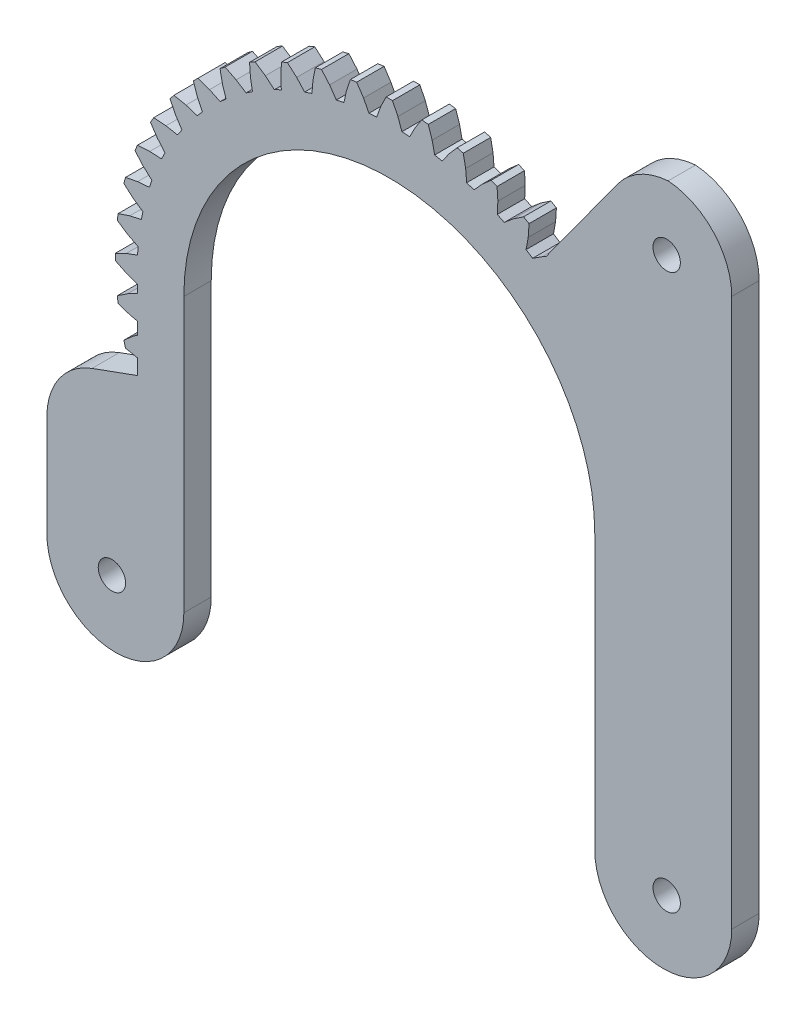
SolidWorks part; units mm, degrees
material "Delrin 2700 NC010, Low Viscosity Acetal Copolymer (SS)"
ref_plane "Front Plane" through (0, 0, 0) normal (0, 0, 1) x (1, 0, 0)
ref_plane "Top Plane" through (0, 0, 0) normal (0, 1, 0) x (1, 0, 0)
ref_plane "Right Plane" through (0, 0, 0) normal (1, 0, 0) x (0, 0, -1)
sketch "Sketch1" plane through (0, 0, 0) normal (0, 0, 1) x (1, 0, 0)
  line L0 (83.8835, 67.191) -> (85.5092, 66.6061)
  line L1 (85.5092, 66.6061) -> (87.1271, 65.8138)
  line L2 (87.1271, 65.8138) -> (87.1271, 64.8854)
  line L3 (87.1271, 64.8854) -> (85.5092, 64.0931)
  line L4 (85.5092, 64.0931) -> (83.8835, 63.5083)
  line L5 (83.8835, 63.5083) -> (83.8095, 62.3776)
  line L6 (83.8095, 62.3776) -> (85.3448, 61.5855)
  line L7 (85.3448, 61.5855) -> (86.8456, 60.5888)
  line L8 (86.8456, 60.5888) -> (86.7243, 59.6683)
  line L9 (86.7243, 59.6683) -> (85.0168, 59.094)
  line L10 (85.0168, 59.094) -> (83.3288, 58.7263)
  line L11 (83.3288, 58.7263) -> (83.1077, 57.615)
  line L12 (83.1077, 57.615) -> (84.5266, 56.6293)
  line L13 (84.5266, 56.6293) -> (85.8844, 55.4453)
  line L14 (85.8844, 55.4453) -> (85.6441, 54.5485)
  line L15 (85.6441, 54.5485) -> (83.8761, 54.202)
  line L16 (83.8761, 54.202) -> (82.1545, 54.0577)
  line L17 (82.1545, 54.0577) -> (81.7903, 52.9848)
  line L18 (81.7903, 52.9848) -> (83.0684, 51.8222)
  line L19 (83.0684, 51.8222) -> (84.26, 50.4711)
  line L20 (84.26, 50.4711) -> (83.9048, 49.6134)
  line L21 (83.9048, 49.6134) -> (82.1066, 49.5006)
  line L22 (82.1066, 49.5006) -> (80.3809, 49.5823)
  line L23 (80.3809, 49.5823) -> (79.8799, 48.5661)
  line L24 (79.8799, 48.5661) -> (80.9952, 47.2468)
  line L25 (80.9952, 47.2468) -> (82.0003, 45.7516)
  line L26 (82.0003, 45.7516) -> (81.5361, 44.9476)
  line L27 (81.5361, 44.9476) -> (79.7387, 45.0704)
  line L28 (79.7387, 45.0704) -> (78.0384, 45.3766)
  line L29 (78.0384, 45.3766) -> (77.4089, 44.4346)
  line L30 (77.4089, 44.4346) -> (78.3426, 42.9809)
  line L31 (78.3426, 42.9809) -> (79.1439, 41.3674)
  line L32 (79.1439, 41.3674) -> (78.5788, 40.6309)
  line L33 (78.5788, 40.6309) -> (76.8128, 40.9873)
  line L34 (76.8128, 40.9873) -> (75.167, 41.5128)
  line L35 (75.167, 41.5128) -> (74.4199, 40.6609)
  line L36 (74.4199, 40.6609) -> (75.1558, 39.0979)
  line L37 (75.1558, 39.0979) -> (75.7397, 37.3936)
  line L38 (75.7397, 37.3936) -> (75.0832, 36.737)
  line L39 (75.0832, 36.737) -> (73.3788, 37.3209)
  line L40 (73.3788, 37.3209) -> (71.8158, 38.0569)
  line L41 (71.8158, 38.0569) -> (70.9639, 37.3097)
  line L42 (70.9639, 37.3097) -> (71.4895, 35.6639)
  line L43 (71.4895, 35.6639) -> (71.8459, 33.898)
  line L44 (71.8459, 33.898) -> (71.1093, 33.3328)
  line L45 (71.1093, 33.3328) -> (69.4958, 34.1341)
  line L46 (69.4958, 34.1341) -> (68.0421, 35.0679)
  line L47 (68.0421, 35.0679) -> (67.1001, 34.4384)
  line L48 (67.1001, 34.4384) -> (67.4064, 32.738)
  line L49 (67.4064, 32.738) -> (67.5292, 30.9407)
  line L50 (67.5292, 30.9407) -> (66.7251, 30.4764)
  line L51 (66.7251, 30.4764) -> (65.23, 31.4815)
  line L52 (65.23, 31.4815) -> (63.9107, 32.5969)
  line L53 (63.9107, 32.5969) -> (62.8945, 32.0958)
  line L54 (62.8945, 32.0958) -> (62.9762, 30.3701)
  line L55 (62.9762, 30.3701) -> (62.8633, 28.572)
  line L56 (62.8633, 28.572) -> (62.0056, 28.2167)
  line L57 (62.0056, 28.2167) -> (60.6545, 29.4083)
  line L58 (60.6545, 29.4083) -> (59.4919, 30.6864)
  line L59 (59.4919, 30.6864) -> (58.419, 30.3222)
  line L60 (58.419, 30.3222) -> (58.2748, 28.6006)
  line L61 (58.2748, 28.6006) -> (57.9283, 26.8327)
  line L62 (57.9283, 26.8327) -> (57.0315, 26.5924)
  line L63 (57.0315, 26.5924) -> (55.8474, 27.9502)
  line L64 (55.8474, 27.9502) -> (54.8618, 29.369)
  line L65 (54.8618, 29.369) -> (53.7504, 29.1479)
  line L66 (53.7504, 29.1479) -> (53.3827, 27.4599)
  line L67 (53.3827, 27.4599) -> (52.8084, 25.7524)
  line L68 (52.8084, 25.7524) -> (51.888, 25.6311)
  line L69 (51.888, 25.6311) -> (50.8913, 27.1319)
  line L70 (50.8913, 27.1319) -> (50.0992, 28.6672)
  line L71 (50.0992, 28.6672) -> (48.9685, 28.5932)
  line L72 (48.9685, 28.5932) -> (48.3836, 26.9675)
  line L73 (48.3836, 26.9675) -> (47.5914, 25.3496)
  line L74 (47.5914, 25.3496) -> (46.6629, 25.3496)
  line L75 (46.6629, 25.3496) -> (45.8707, 26.9675)
  line L76 (45.8707, 26.9675) -> (45.2858, 28.5932)
  line L77 (45.2858, 28.5932) -> (44.1551, 28.6672)
  line L78 (44.1551, 28.6672) -> (43.363, 27.1319)
  line L79 (43.363, 27.1319) -> (42.3663, 25.6311)
  line L80 (42.3663, 25.6311) -> (41.4459, 25.7524)
  line L81 (41.4459, 25.7524) -> (40.8715, 27.4599)
  line L82 (40.8715, 27.4599) -> (40.5038, 29.1479)
  line L83 (40.5038, 29.1479) -> (39.3925, 29.369)
  line L84 (39.3925, 29.369) -> (38.4068, 27.9502)
  line L85 (38.4068, 27.9502) -> (37.2228, 26.5924)
  line L86 (37.2228, 26.5924) -> (36.326, 26.8327)
  line L87 (36.326, 26.8327) -> (35.9795, 28.6006)
  line L88 (35.9795, 28.6006) -> (35.8352, 30.3222)
  line L89 (35.8352, 30.3222) -> (34.7624, 30.6864)
  line L90 (34.7624, 30.6864) -> (33.5998, 29.4083)
  line L91 (33.5998, 29.4083) -> (32.2487, 28.2167)
  line L92 (32.2487, 28.2167) -> (31.3909, 28.572)
  line L93 (31.3909, 28.572) -> (31.2781, 30.3701)
  line L94 (31.2781, 30.3701) -> (31.3598, 32.0958)
  line L95 (31.3598, 32.0958) -> (30.3436, 32.5969)
  line L96 (30.3436, 32.5969) -> (29.0243, 31.4815)
  line L97 (29.0243, 31.4815) -> (27.5292, 30.4764)
  line L98 (27.5292, 30.4764) -> (26.7251, 30.9407)
  line L99 (26.7251, 30.9407) -> (26.8479, 32.738)
  line L100 (26.8479, 32.738) -> (27.1541, 34.4384)
  line L101 (27.1541, 34.4384) -> (26.2121, 35.0679)
  line L102 (26.2121, 35.0679) -> (24.7585, 34.1341)
  line L103 (24.7585, 34.1341) -> (23.1449, 33.3328)
  line L104 (23.1449, 33.3328) -> (22.4084, 33.898)
  line L105 (22.4084, 33.898) -> (22.7648, 35.6639)
  line L106 (22.7648, 35.6639) -> (23.2904, 37.3097)
  line L107 (23.2904, 37.3097) -> (22.4384, 38.0569)
  line L108 (22.4384, 38.0569) -> (20.8754, 37.3209)
  line L109 (20.8754, 37.3209) -> (19.1711, 36.737)
  line L110 (19.1711, 36.737) -> (18.5146, 37.3936)
  line L111 (18.5146, 37.3936) -> (19.0984, 39.0979)
  line L112 (19.0984, 39.0979) -> (19.8344, 40.6609)
  line L113 (19.8344, 40.6609) -> (19.0872, 41.5128)
  line L114 (19.0872, 41.5128) -> (17.4414, 40.9873)
  line L115 (17.4414, 40.9873) -> (15.6755, 40.6309)
  line L116 (15.6755, 40.6309) -> (15.1103, 41.3674)
  line L117 (15.1103, 41.3674) -> (15.9116, 42.9809)
  line L118 (15.9116, 42.9809) -> (16.8454, 44.4346)
  line L119 (16.8454, 44.4346) -> (16.2159, 45.3766)
  line L120 (16.2159, 45.3766) -> (14.5155, 45.0704)
  line L121 (14.5155, 45.0704) -> (12.7182, 44.9476)
  line L122 (12.7182, 44.9476) -> (12.2539, 45.7516)
  line L123 (12.2539, 45.7516) -> (13.2591, 47.2468)
  line L124 (13.2591, 47.2468) -> (14.3744, 48.5661)
  line L125 (14.3744, 48.5661) -> (13.8733, 49.5823)
  line L126 (13.8733, 49.5823) -> (12.1476, 49.5006)
  line L127 (12.1476, 49.5006) -> (10.3495, 49.6134)
  line L128 (10.3495, 49.6134) -> (9.9942, 50.4711)
  line L129 (9.9942, 50.4711) -> (11.1858, 51.8222)
  line L130 (11.1858, 51.8222) -> (12.4639, 52.9848)
  line L131 (12.4639, 52.9848) -> (12.0997, 54.0577)
  line L132 (12.0997, 54.0577) -> (10.3781, 54.202)
  line L133 (10.3781, 54.202) -> (8.6102, 54.5485)
  line L134 (8.6102, 54.5485) -> (8.3699, 55.4453)
  line L135 (8.3699, 55.4453) -> (9.7277, 56.6293)
  line L136 (9.7277, 56.6293) -> (11.1465, 57.615)
  line L137 (11.1465, 57.615) -> (10.9255, 58.7263)
  line L138 (10.9255, 58.7263) -> (9.2374, 59.094)
  line L139 (9.2374, 59.094) -> (7.5299, 59.6683)
  line L140 (7.5299, 59.6683) -> (7.4086, 60.5888)
  line L141 (7.4086, 60.5888) -> (8.9094, 61.5855)
  line L142 (8.9094, 61.5855) -> (10.4448, 62.3776)
  line L143 (10.4448, 62.3776) -> (10.3707, 63.5083)
  line L144 (10.3707, 63.5083) -> (8.745, 64.0931)
  line L145 (8.745, 64.0931) -> (7.1271, 64.8854)
  line L146 (7.1271, 64.8854) -> (7.1271, 65.8138)
  line L147 (7.1271, 65.8138) -> (8.745, 66.6061)
  line L148 (8.745, 66.6061) -> (10.3707, 67.191)
  line L149 (10.3707, 67.191) -> (10.4448, 68.3216)
  line L150 (10.4448, 68.3216) -> (8.9094, 69.1138)
  line L151 (8.9094, 69.1138) -> (7.4086, 70.1105)
  line L152 (7.4086, 70.1105) -> (7.5299, 71.0309)
  line L153 (7.5299, 71.0309) -> (9.2374, 71.6052)
  line L154 (9.2374, 71.6052) -> (10.9255, 71.9729)
  line L155 (10.9255, 71.9729) -> (11.1465, 73.0842)
  line L156 (11.1465, 73.0842) -> (9.7277, 74.0699)
  line L157 (9.7277, 74.0699) -> (8.3699, 75.254)
  line L158 (8.3699, 75.254) -> (8.6102, 76.1508)
  line L159 (8.6102, 76.1508) -> (10.3781, 76.4973)
  line L160 (10.3781, 76.4973) -> (12.0997, 76.6415)
  line L161 (12.0997, 76.6415) -> (12.4639, 77.7144)
  line L162 (12.4639, 77.7144) -> (11.1858, 78.877)
  line L163 (11.1858, 78.877) -> (9.9942, 80.2281)
  line L164 (9.9942, 80.2281) -> (10.3495, 81.0858)
  line L165 (10.3495, 81.0858) -> (12.1476, 81.1987)
  line L166 (12.1476, 81.1987) -> (13.8733, 81.117)
  line L167 (13.8733, 81.117) -> (14.3744, 82.1332)
  line L168 (14.3744, 82.1332) -> (13.2591, 83.4525)
  line L169 (13.2591, 83.4525) -> (12.2539, 84.9476)
  line L170 (12.2539, 84.9476) -> (12.7182, 85.7516)
  line L171 (12.7182, 85.7516) -> (14.5155, 85.6289)
  line L172 (14.5155, 85.6289) -> (16.2159, 85.3226)
  line L173 (16.2159, 85.3226) -> (16.8454, 86.2646)
  line L174 (16.8454, 86.2646) -> (15.9116, 87.7183)
  line L175 (15.9116, 87.7183) -> (15.1103, 89.3318)
  line L176 (15.1103, 89.3318) -> (15.6755, 90.0684)
  line L177 (15.6755, 90.0684) -> (17.4414, 89.712)
  line L178 (17.4414, 89.712) -> (19.0872, 89.1864)
  line L179 (19.0872, 89.1864) -> (19.8344, 90.0383)
  line L180 (19.8344, 90.0383) -> (19.0984, 91.6013)
  line L181 (19.0984, 91.6013) -> (18.5146, 93.3057)
  line L182 (18.5146, 93.3057) -> (19.1711, 93.9622)
  line L183 (19.1711, 93.9622) -> (20.8754, 93.3783)
  line L184 (20.8754, 93.3783) -> (22.4384, 92.6424)
  line L185 (22.4384, 92.6424) -> (23.2904, 93.3895)
  line L186 (23.2904, 93.3895) -> (22.7648, 95.0353)
  line L187 (22.7648, 95.0353) -> (22.4084, 96.8013)
  line L188 (22.4084, 96.8013) -> (23.1449, 97.3664)
  line L189 (23.1449, 97.3664) -> (24.7585, 96.5651)
  line L190 (24.7585, 96.5651) -> (26.2121, 95.6314)
  line L191 (26.2121, 95.6314) -> (27.1541, 96.2609)
  line L192 (27.1541, 96.2609) -> (26.8479, 97.9612)
  line L193 (26.8479, 97.9612) -> (26.7251, 99.7586)
  line L194 (26.7251, 99.7586) -> (27.5292, 100.2228)
  line L195 (27.5292, 100.2228) -> (29.0243, 99.2177)
  line L196 (29.0243, 99.2177) -> (30.3436, 98.1023)
  line L197 (30.3436, 98.1023) -> (31.3598, 98.6034)
  line L198 (31.3598, 98.6034) -> (31.2781, 100.3291)
  line L199 (31.2781, 100.3291) -> (31.3909, 102.1272)
  line L200 (31.3909, 102.1272) -> (32.2487, 102.4825)
  line L201 (32.2487, 102.4825) -> (33.5998, 101.2909)
  line L202 (33.5998, 101.2909) -> (34.7624, 100.0128)
  line L203 (34.7624, 100.0128) -> (35.8352, 100.377)
  line L204 (35.8352, 100.377) -> (35.9795, 102.0986)
  line L205 (35.9795, 102.0986) -> (36.326, 103.8666)
  line L206 (36.326, 103.8666) -> (37.2228, 104.1068)
  line L207 (37.2228, 104.1068) -> (38.4068, 102.7491)
  line L208 (38.4068, 102.7491) -> (39.3925, 101.3302)
  line L209 (39.3925, 101.3302) -> (40.5038, 101.5513)
  line L210 (40.5038, 101.5513) -> (40.8715, 103.2393)
  line L211 (40.8715, 103.2393) -> (41.4459, 104.9468)
  line L212 (41.4459, 104.9468) -> (42.3663, 105.0681)
  line L213 (42.3663, 105.0681) -> (43.363, 103.5673)
  line L214 (43.363, 103.5673) -> (44.1551, 102.032)
  line L215 (44.1551, 102.032) -> (45.2858, 102.106)
  line L216 (45.2858, 102.106) -> (45.8707, 103.7317)
  line L217 (45.8707, 103.7317) -> (46.6629, 105.3496)
  line L218 (46.6629, 105.3496) -> (47.5914, 105.3496)
  line L219 (47.5914, 105.3496) -> (48.3836, 103.7317)
  line L220 (48.3836, 103.7317) -> (48.9685, 102.106)
  line L221 (48.9685, 102.106) -> (50.0992, 102.032)
  line L222 (50.0992, 102.032) -> (50.8913, 103.5673)
  line L223 (50.8913, 103.5673) -> (51.888, 105.0681)
  line L224 (51.888, 105.0681) -> (52.8084, 104.9468)
  line L225 (52.8084, 104.9468) -> (53.3827, 103.2393)
  line L226 (53.3827, 103.2393) -> (53.7504, 101.5513)
  line L227 (53.7504, 101.5513) -> (54.8618, 101.3302)
  line L228 (54.8618, 101.3302) -> (55.8474, 102.7491)
  line L229 (55.8474, 102.7491) -> (57.0315, 104.1068)
  line L230 (57.0315, 104.1068) -> (57.9283, 103.8666)
  line L231 (57.9283, 103.8666) -> (58.2748, 102.0986)
  line L232 (58.2748, 102.0986) -> (58.419, 100.377)
  line L233 (58.419, 100.377) -> (59.4919, 100.0128)
  line L234 (59.4919, 100.0128) -> (60.6545, 101.2909)
  line L235 (60.6545, 101.2909) -> (62.0056, 102.4825)
  line L236 (62.0056, 102.4825) -> (62.8633, 102.1272)
  line L237 (62.8633, 102.1272) -> (62.9762, 100.3291)
  line L238 (62.9762, 100.3291) -> (62.8945, 98.6034)
  line L239 (62.8945, 98.6034) -> (63.9107, 98.1023)
  line L240 (63.9107, 98.1023) -> (65.23, 99.2177)
  line L241 (65.23, 99.2177) -> (66.7251, 100.2228)
  line L242 (66.7251, 100.2228) -> (67.5292, 99.7586)
  line L243 (67.5292, 99.7586) -> (67.4064, 97.9612)
  line L244 (67.4064, 97.9612) -> (67.1001, 96.2609)
  line L245 (67.1001, 96.2609) -> (68.0421, 95.6314)
  line L246 (68.0421, 95.6314) -> (69.4958, 96.5651)
  line L247 (69.4958, 96.5651) -> (71.1093, 97.3664)
  line L248 (71.1093, 97.3664) -> (71.8459, 96.8013)
  line L249 (71.8459, 96.8013) -> (71.4895, 95.0353)
  line L250 (71.4895, 95.0353) -> (70.9639, 93.3895)
  line L251 (70.9639, 93.3895) -> (71.8158, 92.6424)
  line L252 (71.8158, 92.6424) -> (73.3788, 93.3783)
  line L253 (73.3788, 93.3783) -> (75.0832, 93.9622)
  line L254 (75.0832, 93.9622) -> (75.7397, 93.3057)
  line L255 (75.7397, 93.3057) -> (75.1558, 91.6013)
  line L256 (75.1558, 91.6013) -> (74.4199, 90.0383)
  line L257 (74.4199, 90.0383) -> (75.167, 89.1864)
  line L258 (75.167, 89.1864) -> (76.8128, 89.712)
  line L259 (76.8128, 89.712) -> (78.5788, 90.0684)
  line L260 (78.5788, 90.0684) -> (79.1439, 89.3318)
  line L261 (79.1439, 89.3318) -> (78.3426, 87.7183)
  line L262 (78.3426, 87.7183) -> (77.4089, 86.2646)
  line L263 (77.4089, 86.2646) -> (78.0384, 85.3226)
  line L264 (78.0384, 85.3226) -> (79.7387, 85.6289)
  line L265 (79.7387, 85.6289) -> (81.5361, 85.7516)
  line L266 (81.5361, 85.7516) -> (82.0003, 84.9476)
  line L267 (82.0003, 84.9476) -> (80.9952, 83.4525)
  line L268 (80.9952, 83.4525) -> (79.8799, 82.1332)
  line L269 (79.8799, 82.1332) -> (80.3809, 81.117)
  line L270 (80.3809, 81.117) -> (82.1066, 81.1987)
  line L271 (82.1066, 81.1987) -> (83.9048, 81.0858)
  line L272 (83.9048, 81.0858) -> (84.26, 80.2281)
  line L273 (84.26, 80.2281) -> (83.0684, 78.877)
  line L274 (83.0684, 78.877) -> (81.7903, 77.7144)
  line L275 (81.7903, 77.7144) -> (82.1545, 76.6415)
  line L276 (82.1545, 76.6415) -> (83.8761, 76.4973)
  line L277 (83.8761, 76.4973) -> (85.6441, 76.1508)
  line L278 (85.6441, 76.1508) -> (85.8844, 75.254)
  line L279 (85.8844, 75.254) -> (84.5266, 74.0699)
  line L280 (84.5266, 74.0699) -> (83.1077, 73.0842)
  line L281 (83.1077, 73.0842) -> (83.3288, 71.9729)
  line L282 (83.3288, 71.9729) -> (85.0168, 71.6052)
  line L283 (85.0168, 71.6052) -> (86.7243, 71.0309)
  line L284 (86.7243, 71.0309) -> (86.8456, 70.1105)
  line L285 (86.8456, 70.1105) -> (85.3448, 69.1138)
  line L286 (85.3448, 69.1138) -> (83.8095, 68.3216)
  line L287 (83.8095, 68.3216) -> (83.8835, 67.191)
  line L288 (47.1271, 105.3496) -> (47.1271, 25.3496) construction
  line L289 (7.1271, 65.3496) -> (87.1271, 65.3496) construction
  point P292 (47.1271, 65.3496)
sketch "Sketch2" plane through (0, 0, 0) normal (0, 0, 1) x (1, 0, 0)
  line L0 (-2.8729, 47.1511) -> (10.3271, 51.9555)
  line L1 (47.1271, 65.3496) -> (97.1271, 65.3496) construction
  line L2 (47.1271, 65.3496) -> (47.1271, 15.3496) construction
  line L3 (47.1271, 15.3496) -> (97.1271, 15.3496)
  line L4 (97.1271, 65.3496) -> (97.1271, 15.3496)
  line L5 (47.1271, 65.3496) -> (83.4543, 115.3496)
  line L6 (47.1271, 65.3496) -> (47.1271, 15.3496) construction
  line L7 (47.1271, 15.3496) -> (-2.8729, 15.3496)
  line L8 (-2.8729, 47.1511) -> (-2.8729, 15.3496)
  line L9 (47.1271, 65.3496) -> (97.1271, 65.3496) construction
  line L10 (7.1271, 65.3496) -> (87.1271, 65.3496) construction
  line L11 (83.4543, 115.3496) -> (97.1271, 115.3496)
  line L12 (97.1271, 65.3496) -> (97.1271, 115.3496)
  line L13 (47.1271, 105.3496) -> (47.1271, 25.3496) construction
  line L14 (10.3271, 51.9555) -> (10.3271, 65.3496)
  line L15 (10.3271, 65.3496) -> (47.1271, 65.3496)
  line L16 (10.3271, 51.9555) -> (47.1271, 65.3496) construction
  dimension "D1" = 100
  dimension "D2" = 100
  dimension "D3" = 20
  dimension "D4" = 36
  dimension "D5" = 36.8
sketch "Sketch3" plane through (0, 0, 0) normal (0, 0, 1) x (1, 0, 0)
  line L0 (6.6271, 24.8496) -> (-2.8729, 24.8496) construction
  line L1 (-2.8729, 47.1511) -> (-2.8729, 15.3496) construction
  line L2 (6.6271, 24.8496) -> (6.6271, 15.3496) construction
  line L3 (47.1271, 15.3496) -> (-2.8729, 15.3496) construction
  line L4 (47.1271, 65.3496) -> (47.1271, 15.3496) construction
  line L5 (7.1271, 65.3496) -> (87.1271, 65.3496) construction
  line L6 (47.1271, 65.3496) -> (97.1271, 65.3496) construction
  circle A0 centre (6.6271, 24.8496) radius 2
  circle A1 centre (87.6271, 24.8496) radius 2
  circle A2 centre (87.6271, 105.8496) radius 2
  dimension "D1" = 4
  dimension "D2" = 81
sketch "Sketch4" plane through (0, 0, 0) normal (0, 0, 1) x (1, 0, 0)
  circle A0 centre (47.1271, 65.3496) radius 30
  dimension "D1" = 60
extrude "Boss-Extrude1" add sketch "Sketch1" along normal blind 4
extrude "Boss-Extrude2" add sketch "Sketch2" along normal blind 4
extrude "Cut-Extrude1" cut sketch "Sketch3" along normal up to next
extrude "Cut-Extrude2" cut sketch "Sketch4" along normal up to next
sketch "Sketch5" plane through (0, 0, 0) normal (0, 0, 1) x (1, 0, 0)
  line L0 (77.1271, 65.3496) -> (77.1271, 15.3496)
  line L1 (-2.8729, 15.3496) -> (97.1271, 15.3496) construction
  line L2 (17.1271, 65.3496) -> (17.1271, 15.3496)
  line L3 (17.1271, 15.3496) -> (77.1271, 15.3496)
  line L4 (17.1271, 65.3496) -> (77.1271, 65.3496)
  circle A0 centre (47.1271, 65.3496) radius 30 construction
  dimension "D1" = 60
extrude "Cut-Extrude3" cut sketch "Sketch5" along normal up to next
fillet "Fillet1" radius 10 7 edges at (83.4543, 115.3496, 2) (97.1271, 115.3496, 2) (97.1271, 15.3496, 2) (77.1271, 15.3496, 2) (17.1271, 15.3496, 2) (-2.8729, 15.3496, 2) (-2.8729, 47.1511, 2)
